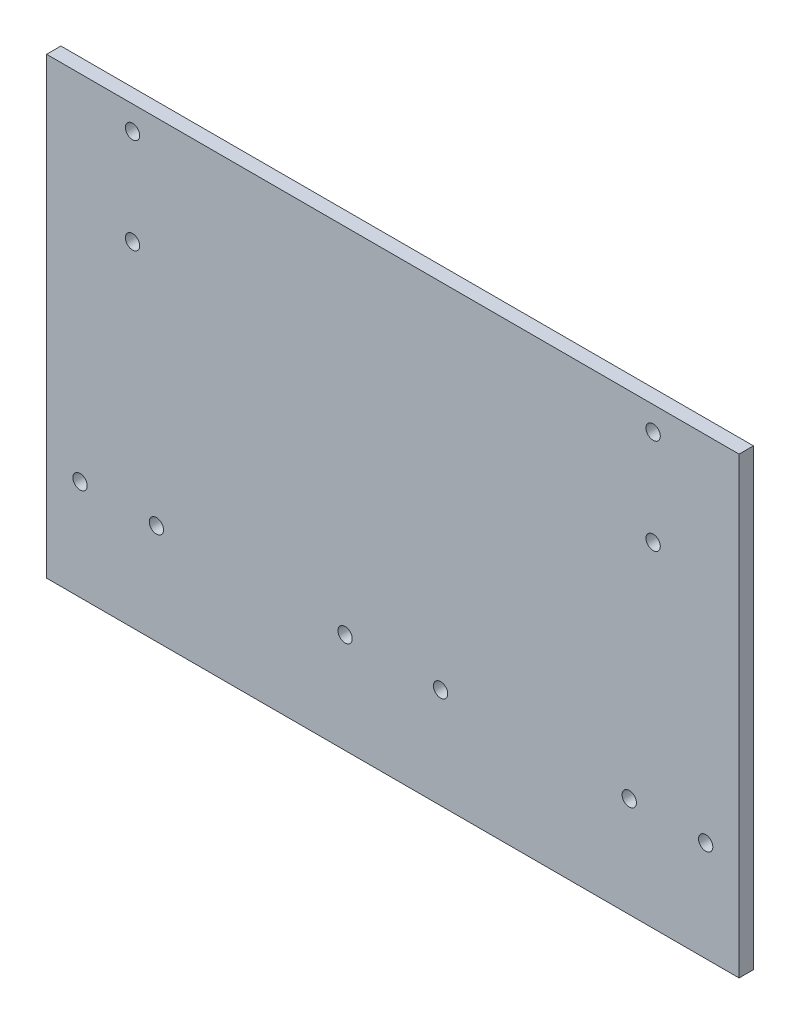
SolidWorks part; units mm, degrees
ref_plane "前视基准面" through (0, 0, 0) normal (0, 0, 1) x (1, 0, 0)
ref_plane "上视基准面" through (0, 0, 0) normal (0, 1, 0) x (1, 0, 0)
ref_plane "右视基准面" through (0, 0, 0) normal (1, 0, 0) x (0, 0, -1)
sketch "草图1" plane through (0, 0, 0) normal (0, 0, 1) x (1, 0, 0)
  line L1 (72.5, -47.5) -> (-72.5, -47.5)
  line L2 (72.5, -47.5) -> (72.5, 47.5)
  line L3 (72.5, 47.5) -> (-72.5, 47.5)
  line L4 (-72.5, -47.5) -> (-72.5, 47.5)
  line L5 (72.5, -47.5) -> (-72.5, 47.5) construction
  line L6 (72.5, 47.5) -> (-72.5, -47.5) construction
  point P0 (0, 0)
  dimension "D1" = 145
  dimension "D2" = 95
extrude "凸台-拉伸1" add sketch "草图1" along normal blind 3
sketch "草图2" plane through (0, 0, 0) normal (0, 0, -1) x (-1, 0, 0)
  line L0 (-72.5, -47.5) -> (-42.5, -47.5) construction
  line L1 (72.5, -47.5) -> (-72.5, -47.5) construction
  line L2 (-57.5, -47.5) -> (-57.5, -26.5) construction
  line L3 (-57.5, -26.5) -> (-49.5, -26.5) construction
  line L4 (0, -47.5) -> (0, 0) construction
  circle A0 centre (-49.5, -26.5) radius 1.5
  circle A1 centre (-65.5, -26.5) radius 1.5
  circle A2 centre (49.5, -26.5) radius 1.5
  circle A3 centre (65.5, -26.5) radius 1.5
  dimension "D1" = 30
  dimension "D3" = 3
  dimension "D2" = 21
  dimension "D4" = 8
extrude "切除-拉伸1" cut sketch "草图2" against normal blind 3
sketch "草图3" plane through (0, 0, 0) normal (0, 0, -1) x (-1, 0, 0)
  line L0 (0, -47.5) -> (0, -26.5) construction
  line L1 (72.5, -47.5) -> (-72.5, -47.5) construction
  line L2 (0, -26.5) -> (10, -26.5) construction
  circle A0 centre (10, -26.5) radius 1.5
  circle A1 centre (-10, -26.5) radius 1.5
  dimension "D1" = 3
  dimension "D2" = 10
  dimension "D3" = 21
extrude "切除-拉伸2" cut sketch "草图3" against normal blind 3
sketch "草图4" plane through (0, 0, 0) normal (0, 0, -1) x (-1, 0, 0)
  line L0 (-72.5, 47.5) -> (-42.5, 47.5) construction
  line L1 (-72.5, 47.5) -> (72.5, 47.5) construction
  line L2 (-42.5, 47.5) -> (-42.5, 17.5) construction
  line L3 (-42.5, 32.5) -> (-54.5, 32.5) construction
  line L4 (-54.5, 32.5) -> (-54.5, 42.5) construction
  line L5 (0, 1.65) -> (0, -1.65) construction
  circle A0 centre (-54.5, 42.5) radius 1.5
  circle A1 centre (-54.5, 22.5) radius 1.5
  circle A2 centre (54.5, 22.5) radius 1.5
  circle A3 centre (54.5, 42.5) radius 1.5
  dimension "D3" = 12
  dimension "D4" = 3
  dimension "D1" = 30
  dimension "D2" = 30
  dimension "D5" = 10
extrude "切除-拉伸4" cut sketch "草图4" against normal blind 3
